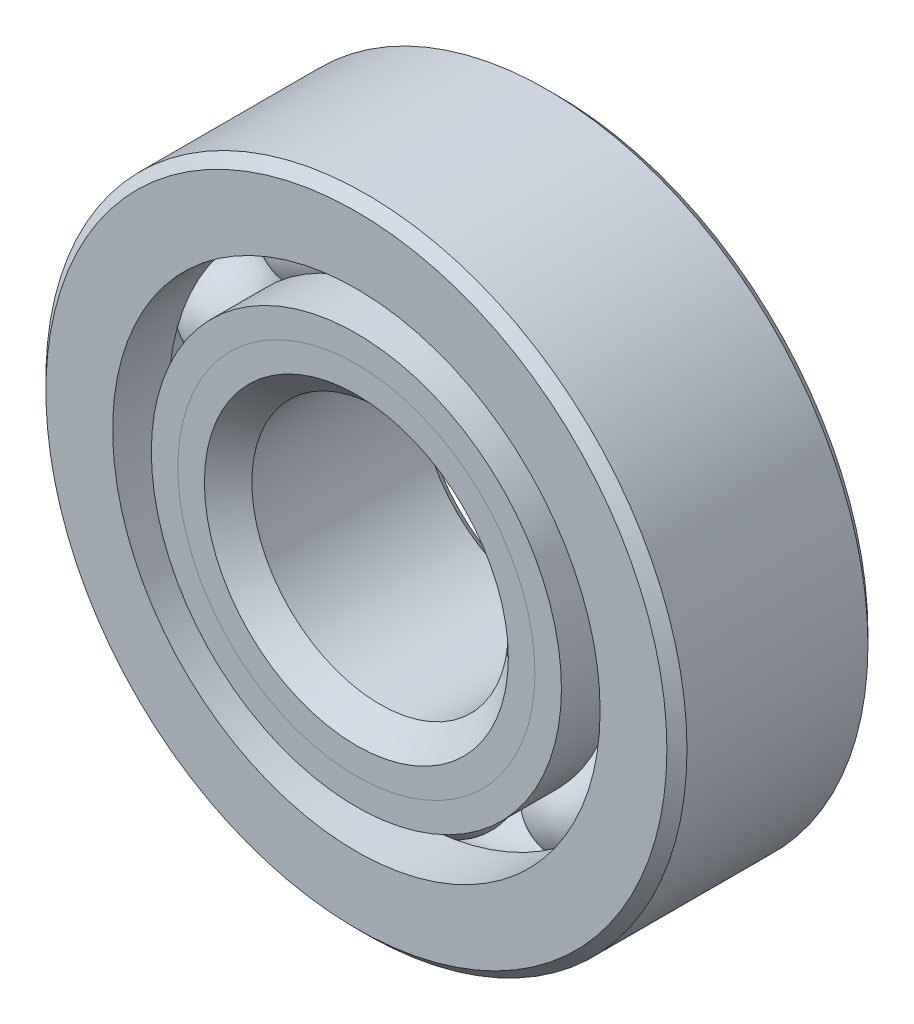
SolidWorks part; units mm, degrees
material "ABS"
ref_plane "Front Plane" through (0, 0, 0) normal (0, 0, 1) x (1, 0, 0)
ref_plane "Top Plane" through (0, 0, 0) normal (0, 1, 0) x (1, 0, 0)
ref_plane "Right Plane" through (0, 0, 0) normal (1, 0, 0) x (0, 0, -1)
sketch "Sketch1" plane through (0, 0, 0) normal (1, 0, 0) x (0, 0, -1)
  line L0 (-2.4892, 0) -> (2.4892, 0) construction
  line L1 (0, 7.9375) -> (0, -7.9375) construction
  line L2 (2.2403, 7.9375) -> (-2.2403, 7.9375)
  line L3 (-2.2403, 7.9375) -> (-2.4892, 7.6886)
  line L4 (-2.4892, 7.6886) -> (-2.4892, 6.0352)
  line L5 (-2.4892, 6.0352) -> (-1.1063, 6.0352)
  line L6 (2.4892, 6.0352) -> (1.1063, 6.0352)
  line L7 (2.4892, 7.6886) -> (2.4892, 6.0352)
  line L8 (2.2403, 7.9375) -> (2.4892, 7.6886)
  line L9 (0, 7.9375) -> (0, 5.5563) construction
  line L10 (0, 5.5563) -> (0, 3.175) construction
  arc A0 (-1.1063, 6.0352) -> (1.1063, 6.0352) centre (0, 5.5563) cw
  point P14 (0, 3.175)
  dimension "Width" = 4.9784
  dimension "OD" = 15.875
  dimension "D1" = 45
  dimension "D2" = 0.2489
  dimension "D3" = 2.2126
  dimension "D4" = 0.479
revolve "Revolve1" add sketch "Sketch1" angle 360 about L0
sketch "Sketch2" plane through (0, 0, 0) normal (1, 0, 0) x (0, 0, -1)
  line L0 (-2.4892, 5.0773) -> (-1.1063, 5.0773)
  line L1 (-2.4892, 7.6886) -> (-2.4892, -7.6886) construction
  line L2 (-2.4892, 5.0773) -> (-2.4892, 4.4201)
  line L3 (-2.4892, 4.4201) -> (-1.832, 3.7629)
  line L4 (-1.832, 3.7629) -> (0, 3.7629)
  line L5 (0, 7.9375) -> (0, -7.9375) construction
  line L6 (0, 3.7629) -> (0, 4.3507)
  line L7 (0, 4.3507) -> (0, 3.175) construction
  line L8 (-2.4892, 5.0773) -> (-2.4892, 3.7629) construction
  line L9 (-2.4892, 3.7629) -> (-1.832, 3.7629) construction
  arc A0 (-1.1063, 5.0773) -> (0, 4.3507) centre (0, 5.5563) ccw
  arc A1 (1.1063, 6.0352) -> (-1.1063, 6.0352) centre (0, 5.5563) ccw construction
  circle A2 centre (0, 5.5563) radius 1.2055 construction
  dimension "D1" = 45
revolve "Revolve2" add sketch "Sketch2" angle 360 about L0
sketch "Sketch3" plane through (0, 0, 0) normal (1, 0, 0) x (0, 0, -1)
  line L0 (-2.4892, 4.4201) -> (-1.832, 3.7629)
  line L1 (-1.832, 3.7629) -> (0, 3.7629)
  line L2 (0, 3.7629) -> (0, 4.3507)
  line L3 (-2.4892, 4.4201) -> (-2.4892, 3.7629)
  line L4 (-2.4892, 5.0773) -> (-2.4892, 3.7629) construction
  line L5 (-2.4892, 3.7629) -> (-1.9013, 3.175)
  line L6 (-1.9013, 3.175) -> (2.2403, 3.175)
  line L7 (2.2403, 7.9375) -> (2.2403, -7.9375) construction
  line L8 (2.2403, 3.175) -> (2.4892, 3.4239)
  line L9 (2.4892, -7.6886) -> (2.4892, 7.6886) construction
  line L10 (2.4892, 3.4239) -> (2.4892, 5.0773)
  line L11 (2.4892, 5.0773) -> (1.1063, 5.0773)
  line L13 (2.2403, 7.9375) -> (2.4892, 7.6886) construction
  circle A0 centre (0, 5.5563) radius 1.2055 construction
  arc A1 (1.1063, 5.0773) -> (0, 4.3507) centre (0, 5.5563) cw
revolve "Revolve3" add sketch "Sketch3" angle 360 about L0
sketch "Sketch4" plane through (0, 0, 0) normal (1, 0, 0) x (0, 0, -1)
  line L0 (-1.2055, 5.5563) -> (1.2055, 5.5563)
  circle A1 centre (0, 5.5563) radius 1.2055 construction
  arc A2 (-1.2055, 5.5563) -> (1.2055, 5.5563) centre (0, 5.5563) cw
  arc A3 (1.1063, 6.0352) -> (-1.1063, 6.0352) centre (0, 5.5563) ccw construction
revolve "Revolve4" add sketch "Sketch4" angle 360 about L0
ref_axis "Axis1" through (0, 0, -2.4892) along (0, 0, 1)
pattern_circular "CirPattern1" count 10 every 36 about axis through (0, 0, -2.4892) along (0, 0, 1) of bodies 104
equation "\"D2@Sketch1\" = \"Width@Sketch1\"*.05"
equation "\"D3@Sketch1\" = \"Width@Sketch1\"/2.25"
equation "\"D4@Sketch1\" = (((\"OD@Sketch1\"-\"Width@Sketch1\")/2)/3.25)/3.5"
equation "\"D2@CirPattern1\" = 360/\"Balls@CirPattern1\""
